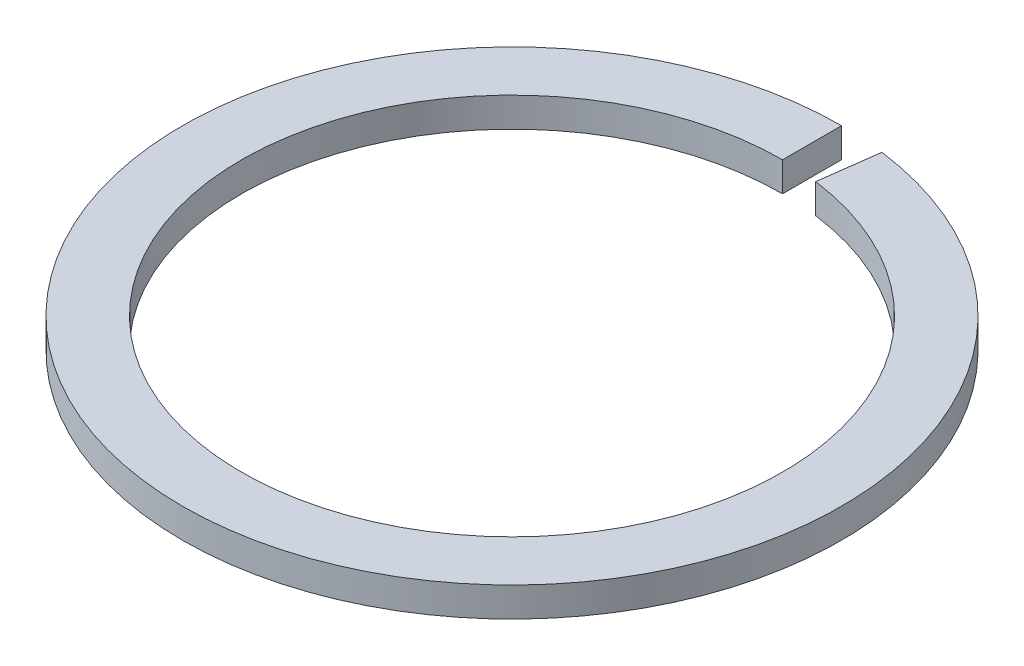
SolidWorks part; units mm, degrees
material "Stainless Steel (ferritic)"
ref_plane "Front Plane" through (0, 0, 0) normal (0, 0, 1) x (1, 0, 0)
ref_plane "Top Plane" through (0, 0, 0) normal (0, 1, 0) x (1, 0, 0)
ref_plane "Right Plane" through (0, 0, 0) normal (1, 0, 0) x (0, 0, -1)
sketch "Sketch1" plane through (0, 0, 0) normal (1, 0, 0) x (0, 0, -1)
  line L1 (-0.75, -0.375) -> (0.75, -0.375)
  line L2 (-0.75, -0.375) -> (-0.75, 0.375)
  line L3 (-0.75, 0.375) -> (0.75, 0.375)
  line L4 (0.75, -0.375) -> (0.75, 0.375)
  line L5 (-0.75, -0.375) -> (0.75, 0.375) construction
  line L6 (-0.75, 0.375) -> (0.75, -0.375) construction
  point P0 (0, 0)
  dimension "D1" = 1.5
  dimension "D2" = 0.75
sketch "Sketch2" plane through (0, 0, 0) normal (0, 1, 0) x (1, 0, 0)
  line L0 (0, 1.4334) -> (0, -15.6617) construction
  line L1 (1, 1.4334) -> (1, -15.8062) construction
  arc A2 (0, 0) -> (1, -0.0659) centre (0, -7.625) ccw
  dimension "D1" = 7.625
  dimension "D2" = 1
  dimension "15.25" = 15.25
sweep "Sweep1" add profiles "Sketch1" path "Sketch2"
